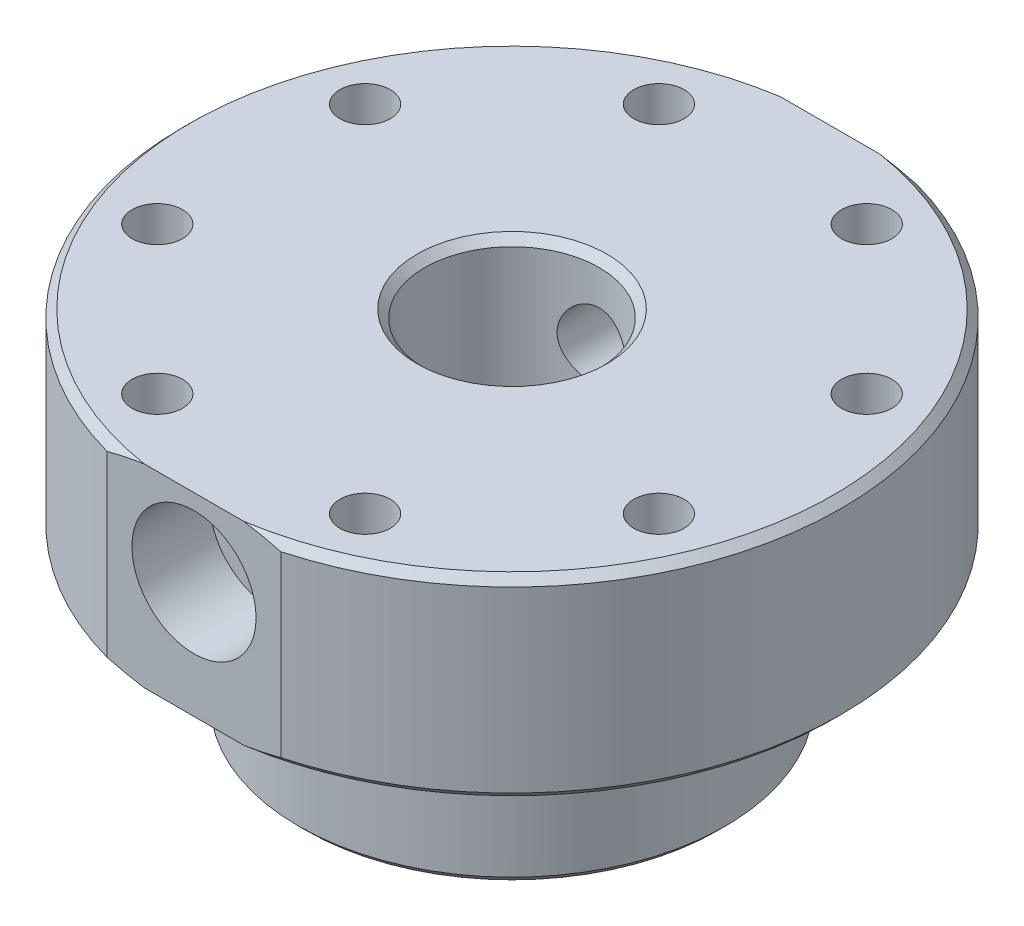
SolidWorks part; units mm, degrees
ref_plane "前基準面" through (0, 0, 0) normal (0, 0, 1) x (1, 0, 0)
ref_plane "上基準面" through (0, 0, 0) normal (0, 1, 0) x (1, 0, 0)
ref_plane "右基準面" through (0, 0, 0) normal (1, 0, 0) x (0, 0, -1)
sketch "草圖1" plane through (0, 0, 0) normal (0, 1, 0) x (1, 0, 0)
  circle A0 centre (0, 0) radius 85
  dimension "D1" = 170
extrude "填料-伸長1" add sketch "草圖1" along normal blind 50
hole_wizard "M12 六角頭螺栓的柱孔1" positions "草圖5" profile "草圖4" counterbore size "M12" standard "Ansi 公制" end condition through all
sketch "草圖5" plane through (0, 0, 0) normal (0, -1, 0) x (1, 0, 0)
  line L0 (-85, 0) -> (85, 0) construction
  line L2 (0, 0) -> (-64.6716, 26.7878) construction
  circle A0 centre (0, 0) radius 70 construction
  circle A1 centre (0, 0) radius 85 construction
  point P0 (-64.6716, 26.7878)
  dimension "D1" = 140
  dimension "D2" = 22.5
sketch "草圖4" plane through (-64.6716, 0, 26.7878) normal (1, 0, 0) x (0, 0, -1)
  line L0 (0, 0) -> (0, 50)
  line L1 (0, 50) -> (6.5, 50)
  line L3 (6.5, 50) -> (6.5, 15)
  line L4 (6.5, 15) -> (11, 15)
  line L5 (11, 15) -> (11, 0)
  line L7 (11, 0) -> (0, 0)
  line L11 (0, -6.35) -> (0, 107.95) construction
  dimension "貫穿孔直徑" = 13
  dimension "貫穿孔深度" = 50
  dimension "柱孔直徑" = 22
  dimension "柱孔深度" = 15
pattern_circular "環狀複製排列1" count 8 over 360 about axis through (0, 50, 0) along (0, -1, 0) of "M12 六角頭螺栓的柱孔1"
sketch "草圖6" plane through (0, 50, 0) normal (0, 1, 0) x (1, 0, 0)
  line L0 (-1000, 0) -> (49000, 0) construction
  line L2 (-22.383, 82) -> (22.383, 82)
  line L3 (-22.383, 82) -> (-22.383, 91.0838)
  line L4 (-22.383, 91.0838) -> (22.383, 91.0838)
  line L5 (22.383, 82) -> (22.383, 91.0838)
  line L6 (-22.383, -82) -> (22.383, -82)
  line L7 (-22.383, -82) -> (-22.383, -90.1474)
  line L8 (-22.383, -90.1474) -> (22.383, -90.1474)
  line L9 (22.383, -82) -> (22.383, -90.1474)
  circle A0 centre (0, 0) radius 85 construction
  dimension "D1" = 164
extrude "除料-伸長1" cut sketch "草圖6" against normal through all
sketch "草圖7" plane through (0, 0, -82) normal (0, 0, -1) x (-1, 0, 0)
  line L0 (0, -1000) -> (0, 49000) construction
  line L1 (22.383, 0) -> (-22.383, 0) construction
  circle A0 centre (0, 30) radius 16
  point P5 (0, 0)
  dimension "D1" = 32
  dimension "D2" = 30
extrude "除料-伸長2" cut sketch "草圖7" against normal blind 20
mirror "鏡射1" about plane through (0, 0, 0) normal (0, 0, 1) of "除料-伸長2"
sketch "草圖8" plane through (0, 0, 62) normal (0, 0, 1) x (1, 0, 0)
  circle A0 centre (0, 30) radius 9
  dimension "D1" = 18
extrude "除料-伸長3" cut sketch "草圖8" against normal through all
chamfer "導角1" distance 2 angle 45 4 edges at (-85, 0, 0) (85, 0, 0) (-85, 50, 0) (85, 50, 0)
sketch "草圖9" plane through (0, 0, 0) normal (0, -1, 0) x (1, 0, 0)
  circle A0 centre (0, 0) radius 55
  dimension "D1" = 110
extrude "填料-伸長2" add sketch "草圖9" along normal blind 40
sketch "草圖10" plane through (0, -40, 0) normal (0, -1, 0) x (1, 0, 0)
  circle A0 centre (0, 0) radius 22.5
  dimension "D1" = 45
extrude "除料-伸長4" cut sketch "草圖10" against normal through all
sketch "草圖11" plane through (0, 0, 0) normal (0, 0, 1) x (1, 0, 0)
  line L0 (-22.5, 50) -> (-22.5, -40) construction
  line L1 (-22.5, -24) -> (-24, -24)
  line L2 (-22.5, -24) -> (-22.5, -27)
  line L3 (-22.5, -27) -> (-24, -27)
  line L4 (-24, -24) -> (-24, -27)
  line L5 (-55, -40) -> (55, -40) construction
  line L6 (-22.5, -16) -> (-24, -16)
  line L7 (-22.5, -16) -> (-22.5, -19)
  line L8 (-22.5, -19) -> (-24, -19)
  line L9 (-24, -16) -> (-24, -19)
  line L10 (-22.5, -32) -> (-24, -32)
  line L11 (-22.5, -32) -> (-22.5, -35)
  line L12 (-22.5, -35) -> (-24, -35)
  line L13 (-24, -32) -> (-24, -35)
  line L14 (0, -1030.4932) -> (0, 48969.5068) construction
  line L18 (-22.5, -11) -> (-24, -11)
  line L19 (-22.5, -11) -> (-22.5, -8)
  line L20 (-22.5, -8) -> (-24, -8)
  line L21 (-24, -11) -> (-24, -8)
  line L22 (-22.5, -3) -> (-24, -3)
  line L23 (-22.5, -3) -> (-22.5, 0)
  line L24 (-22.5, 0) -> (-24, 0)
  line L25 (-24, -3) -> (-24, 0)
  dimension "D1" = 3
  dimension "D2" = 5
  dimension "D3" = 5
  dimension "D4" = 5
  dimension "D5" = 1.5
  dimension "D6" = 5
  dimension "D7" = 5
revolve "除料-旋轉1" cut sketch "草圖11" angle 360 about L14
chamfer "導角2" distance 5 angle 45 1 edges at (0, -40, -22.5)
chamfer "導角3" distance 2 angle 45 1 edges at (0, -40, -55)
chamfer "導角4" distance 2 angle 45 1 edges at (0, 50, -22.5)
